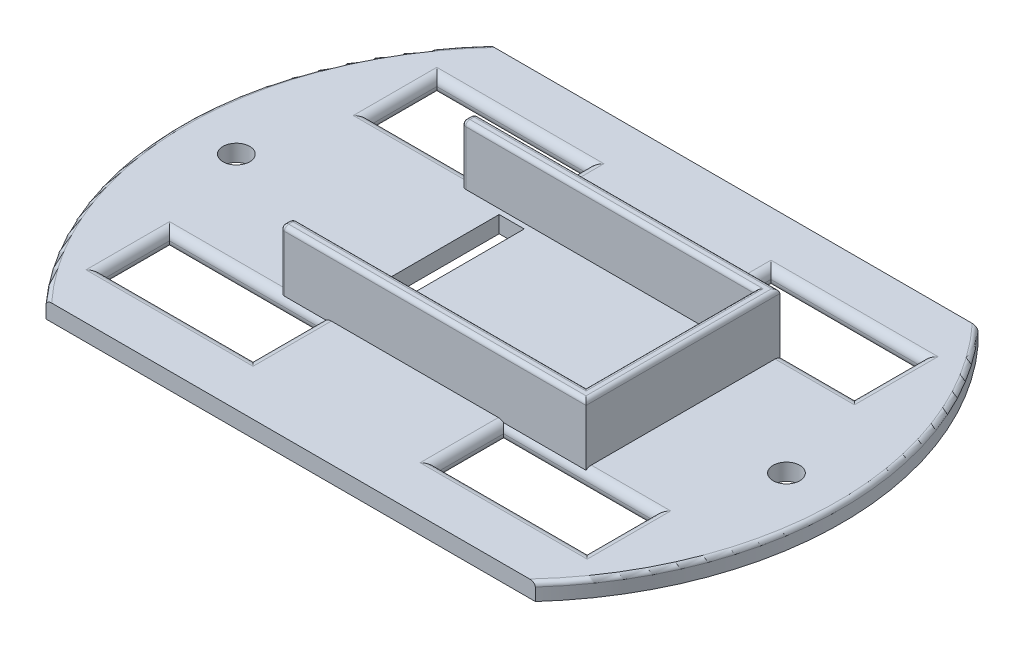
SolidWorks part; units mm, degrees
ref_plane "Płaszczyzna przednia" through (0, 0, 0) normal (0, 0, 1) x (1, 0, 0)
ref_plane "Płaszczyzna górna" through (0, 0, 0) normal (0, 1, 0) x (1, 0, 0)
ref_plane "Płaszczyzna prawa" through (0, 0, 0) normal (1, 0, 0) x (0, 0, -1)
sketch "Sketch1" plane through (0, 0, 0) normal (0, 1, 0) x (1, 0, 0)
  line L8 (0.0031, 0.031) -> (0.0031, 39.531)
  line L9 (0.0031, 0.031) -> (0.0031, -39.469)
  line L11 (0.0031, 39.531) -> (0.0031, 26.531)
  line L14 (0.0031, 26.531) -> (29.2948, 26.531)
  line L15 (29.2948, 26.531) -> (-29.2885, 26.531)
  line L16 (29.2948, 26.531) -> (29.2948, -26.469)
  line L17 (29.2948, -26.469) -> (-29.2885, -26.469)
  circle A0 centre (0.0031, 0.031) radius 39.5
  point P0 (0, 0)
extrude "Boss-Extrude1" add sketch "Sketch1" along normal blind 2 contours A0 | A0 | L16 A0 | L17 L16 L14 L8 L9 | L15 A0 L17 L9 L8 region at (-18.2661, 0, -0.031) region at (14.6489, 0, -0.031) region at (33.427, 0, -0.031)
sketch "Sketch2" plane through (0, 0, 0) normal (0, -1, 0) x (1, 0, 0)
  line L0 (0, 0) -> (-8, 0)
  line L6 (-8, 0) -> (-8, 9.5)
  line L7 (-8, 9.5) -> (-11, 9.5)
  line L8 (-11, 9.5) -> (-11, -9.5)
  line L9 (-11, -9.5) -> (-8, -9.5)
  line L10 (-8, -9.5) -> (-8, 0)
extrude "Cut-Extrude1" cut sketch "Sketch2" against normal blind 22 contours L6 L7 L8 L9 L10
sketch "Sketch3" plane through (0, 2, 0) normal (0, 1, 0) x (1, 0, 0)
  line L0 (2.9, 0) -> (2.9, 10.1)
  line L1 (2.9, 10.1) -> (19, 10.1)
  line L2 (19, 10.1) -> (19, -10.1)
  line L3 (19, -10.1) -> (-14.6, -10.1)
  line L4 (-14.6, -10.1) -> (-14.6, 10.1)
  line L5 (-14.6, 10.1) -> (2.9, 10.1)
  line L6 (2.9, 10.1) -> (2.9, 11.6)
  line L7 (19, 10.1) -> (20.5, 10.1)
  line L8 (19, -10.1) -> (19, -11.6)
  line L9 (-14.6, -10.1) -> (-16.1, -10.1)
  line L10 (2.9, 11.6) -> (20.5, 11.6)
  line L11 (20.5, 11.6) -> (20.5, -11.6)
  line L12 (20.5, -11.6) -> (-16.1, -11.6)
  line L13 (-16.1, -11.6) -> (-16.1, 11.6)
  line L14 (-16.1, 11.6) -> (2.9, 11.6)
  line L15 (-14.6, 10.1) -> (-16.1, 10.1)
extrude "Boss-Extrude2" add sketch "Sketch3" along normal blind 7 contours L11 L10 L6 L1 L7 | L12 L11 L7 L2 L8 | L13 L12 L8 L3 L9 | L15 L5 L6 L14 L13 region at (11.7, 2, -10.85) region at (-6.6, 2, -10.85) region at (19.75, 2, 0.75) region at (1.45, 2, 10.85)
sketch "Sketch4" plane through (0, 0, 0) normal (0, -1, 0) x (1, 0, 0)
  line L0 (0, 0) -> (-8, 0)
  line L1 (-8, -9.5) -> (-8, 9.5) construction
  line L2 (-8, 0) -> (-8.023, 9.319)
  line L3 (-8.023, 9.319) -> (-3, 9.319)
  line L4 (-3, 9.319) -> (-3, -9.5)
  line L5 (-3, -9.5) -> (-8, -9.5)
  line L6 (-8, -9.5) -> (-8, 0)
extrude "Boss-Extrude3" add sketch "Sketch4" along normal blind 6 contours L2 L3 L4 L5 L6
sketch "Sketch5" plane through (-8, 0, 0) normal (-1, 0, 0) x (0, 0, 1)
  line L0 (0, 0) -> (0, -6)
  line L3 (-26.531, 0) -> (26.469, 0) construction
  line L5 (0, -6) -> (0, 0) construction
  circle A1 centre (-5.031, -2.35) radius 2.25
  circle A4 centre (5.031, -2.35) radius 2.25
extrude "Cut-Extrude3" cut sketch "Sketch5" against normal blind 37 and the other way blind 37 contours A1 | A4 region at (-8, -2.35, -5.031) region at (-8, -2.35, 5.031)
fillet "Fillet1" radius 3 2 edges at (-5.5, -6, -9.5) (-5.5115, -6, 9.319)
fillet "Fillet2" radius 0.5 2 edges at (39.5031, 2, -0.031) (-39.4969, 2, -0.031)
sketch "Sketch6" plane through (0, 0, 0) normal (0, -1, 0) x (1, 0, 0)
  line L0 (0.0031, -0.031) -> (-32.9969, -0.031)
  line L1 (0.0031, -0.031) -> (-0.0115, 6.969)
  circle A0 centre (-32.9969, -0.031) radius 1.6
  circle A1 centre (33.0028, 0.1067) radius 1.6
  dimension "D1" = 33
extrude "Cut-Extrude4" cut sketch "Sketch6" against normal blind 37 contours A0 | A1 region at (-34.5516, 0, -0.031) region at (33.0028, 0, 0.1067)
fillet "Fillet3" radius 0.5 6 edges at (20.5, 9, 0) (19, 9, 0) (1.45, 9, -10.1) (2.2, 9, -11.6) (2.2, 9, 11.6) (1.45, 9, 10.1)
fillet "Fillet4" radius 0.5 10 edges at (-16.1, 5.25, 11.6) (-16.1, 8.8536, 11.4536) (-16.1, 9, 10.85) (-16.1, 8.8536, 10.2464) (-16.1, 5.25, -10.1) (-16.1, 8.8536, -10.2464) (-16.1, 9, -10.85) (-16.1, 8.8536, -11.4536) (-16.1, 5.25, 10.1) (-16.1, 5.25, -11.6)
sketch "Sketch7" plane through (0, 0, 0) normal (0, -1, 0) x (1, 0, 0)
  line L0 (0.0031, -0.031) -> (20.0031, -0.031)
  line L1 (20.0031, -0.031) -> (20.0031, 14.969)
  line L2 (20.0031, 14.969) -> (20.0031, 19.969)
  line L3 (20.0031, 19.969) -> (11.0031, 19.969)
  line L4 (11.0031, 19.969) -> (11.0031, 11.969)
  line L5 (11.0031, 11.969) -> (29.0031, 11.969)
  line L6 (29.0031, 11.969) -> (29.0031, 19.969)
  line L7 (29.0031, 19.969) -> (20.0031, 19.969)
  line L8 (0.0031, -0.031) -> (0.0031, 13.3164)
  line L9 (29.0031, -20.031) -> (20.0031, -20.031)
  line L10 (29.0031, -12.031) -> (29.0031, -20.031)
  line L11 (11.0031, -12.031) -> (29.0031, -12.031)
  line L12 (11.0031, -20.031) -> (11.0031, -12.031)
  line L13 (20.0031, -20.031) -> (11.0031, -20.031)
  line L14 (-28.9969, -12.031) -> (-28.9969, -20.031)
  line L15 (-10.9969, -12.031) -> (-28.9969, -12.031)
  line L16 (-10.9969, -20.031) -> (-10.9969, -12.031)
  line L17 (-19.9969, -20.031) -> (-10.9969, -20.031)
  line L18 (-28.9969, -20.031) -> (-19.9969, -20.031)
  line L19 (-28.9969, 19.969) -> (-19.9969, 19.969)
  line L20 (-28.9969, 11.969) -> (-28.9969, 19.969)
  line L21 (-10.9969, 11.969) -> (-28.9969, 11.969)
  line L22 (-10.9969, 19.969) -> (-10.9969, 11.969)
  line L23 (-19.9969, 19.969) -> (-10.9969, 19.969)
extrude "Cut-Extrude5" cut sketch "Sketch7" against normal blind 10 contours L23 L19 L20 L21 L22 | L4 L5 L1 L2 L3 | L6 L7 L2 L1 L5 | L14 L18 L17 L16 L15 | L13 L9 L10 L11 L12 region at (15.5031, 0, 15.969) region at (24.5031, 0, 15.969) region at (20.0031, 0, -16.031) region at (-19.9969, 0, -16.031) region at (-19.9969, 0, 15.969)
fillet "Fillet7" radius 1 16 edges at (-19.9969, 2, 19.969) (-10.9969, 2, 15.969) (-28.9969, 2, 15.969) (-19.9969, 2, 11.969) (20.0031, 2, 19.969) (11.0031, 2, 15.969) (20.0031, 2, 11.969) (29.0031, 2, 15.969) (-28.9969, 2, -16.031) (-19.9969, 2, -12.031) (-10.9969, 2, -16.031) (-19.9969, 2, -20.031) (11.0031, 2, -16.031) (20.0031, 2, -20.031) (29.0031, 2, -16.031) (20.0031, 2, -12.031)
fillet "Fillet8" radius 1 16 edges at (11.0031, 0, 15.969) (20.0031, 0, 11.969) (29.0031, 0, 15.969) (20.0031, 0, 19.969) (20.0031, 0, -12.031) (29.0031, 0, -16.031) (20.0031, 0, -20.031) (11.0031, 0, -16.031) (-10.9969, 0, 15.969) (-19.9969, 0, 19.969) (-28.9969, 0, 15.969) (-19.9969, 0, 11.969) (-28.9969, 0, -16.031) (-19.9969, 0, -12.031) (-19.9969, 0, -20.031) (-10.9969, 0, -16.031)
